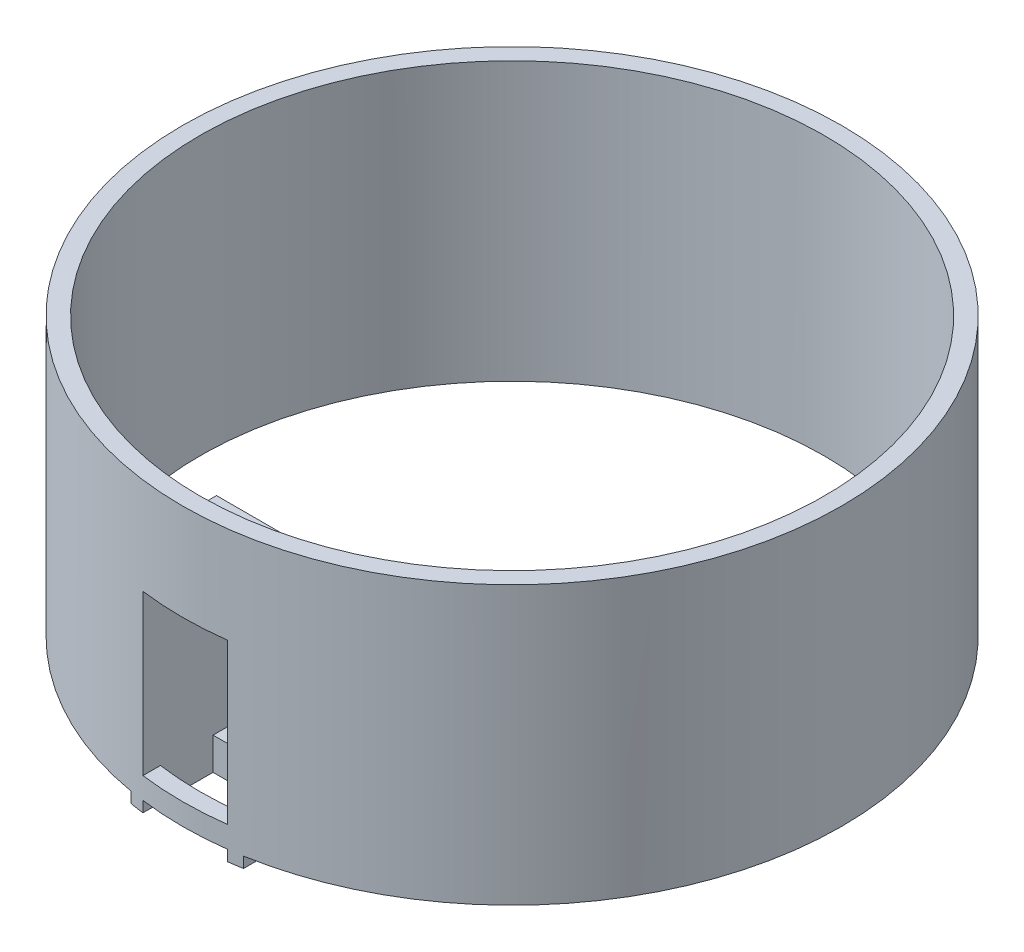
SolidWorks part; units mm, degrees
ref_plane "Ebene vorne" through (0, 0, 0) normal (0, 0, 1) x (1, 0, 0)
ref_plane "Ebene oben" through (0, 0, 0) normal (0, 1, 0) x (1, 0, 0)
ref_plane "Ebene rechts" through (0, 0, 0) normal (1, 0, 0) x (0, 0, -1)
sketch "Sketch1" plane through (0, 0, 0) normal (0, 1, 0) x (1, 0, 0)
  circle A0 centre (0, 0) radius 45
  dimension "D1" = 90
extrude "Extrude-Thin1" add sketch "Sketch1" along normal mid plane 40 thin thin type one direction wall 2.5
ref_plane "Plane1" through (0, 0, 34.5) normal (0, 0, 1) x (1, 0, 0)
sketch "Sketch2" plane through (0, 0, 34.5) normal (0, 0, 1) x (1, 0, 0)
  line L0 (0, 24.763) -> (0, -42.5836) construction
  line L1 (-8.1, -21.55) -> (-8.1, 10.75)
  line L2 (-42.8624, -5.4) -> (35.5776, -5.4) construction
  line L3 (-6.1, 10.75) -> (-6.1, -21.55)
  line L4 (-8.1, 10.75) -> (-6.1, 10.75)
  line L5 (-8.1, -21.55) -> (-6.1, -21.55)
  line L6 (8.1, -21.55) -> (6.1, -21.55)
  line L7 (6.1, 10.75) -> (6.1, -21.55)
  line L8 (8.1, 10.75) -> (6.1, 10.75)
  line L9 (8.1, -21.55) -> (8.1, 10.75)
  point P4 (0, -5.4)
  point P10 (-6.1, -5.4)
  point P11 (-8.1, -5.4)
  dimension "D1" = 5.4
  dimension "D2" = 2
  dimension "D3" = 6.1
  dimension "D4" = 16.15
extrude "Boss-Extrude1" add sketch "Sketch2" along normal up to surface (12.3043 mm away) up to face at (47.5, 20, 0)
sketch "Sketch3" plane through (0, 0, 34.5) normal (0, 0, 1) x (1, 0, 0)
  line L0 (-6.1, -21.55) -> (6.1, -21.55)
  line L1 (6.1, -21.55) -> (6.1, -16.9)
  line L2 (6.1, 10.75) -> (6.1, -21.55) construction
  line L3 (6.1, -16.9) -> (-6.1, -16.9)
  line L4 (-6.1, 10.75) -> (-6.1, -21.55) construction
  line L5 (-6.1, -16.9) -> (-6.1, -21.55)
  line L6 (0, 24.763) -> (0, -42.5836) construction
  line L7 (-16.2671, -5.4) -> (13.1898, -5.4) construction
  line L8 (-42.8624, -5.4) -> (35.5776, -5.4) construction
  line L9 (6.1, 10.75) -> (6.1, 6.1)
  line L10 (-6.1, 10.75) -> (6.1, 10.75)
  line L11 (-6.1, 6.1) -> (-6.1, 10.75)
  line L12 (6.1, 6.1) -> (-6.1, 6.1)
  circle A0 centre (0, -19.55) radius 1.1
  circle A1 centre (0, 8.75) radius 1.1
  dimension "D2" = 2.2
  dimension "D1" = 4.65
  dimension "D3" = 2.65
extrude "Boss-Extrude2" add sketch "Sketch3" along normal blind 2.5
sketch "Sketch4" plane through (0, 0, 34.5) normal (0, 0, 1) x (1, 0, 0)
  line L0 (6.1, -16.9) -> (-6.1, -16.9) construction
  line L1 (6.1, 10.75) -> (6.1, -21.55) construction
  line L2 (6.1, 6.1) -> (-6.1, 6.1) construction
  line L3 (-6.1, 10.75) -> (-6.1, -21.55) construction
  line L4 (6.1, -16.9) -> (-6.1, -16.9)
  line L5 (6.1, 6.1) -> (6.1, -16.9)
  line L6 (6.1, 6.1) -> (-6.1, 6.1)
  line L7 (-6.1, 6.1) -> (-6.1, -16.9)
extrude "Cut-Extrude1" cut sketch "Sketch4" along normal through all contours L5 L4 L7 L6
